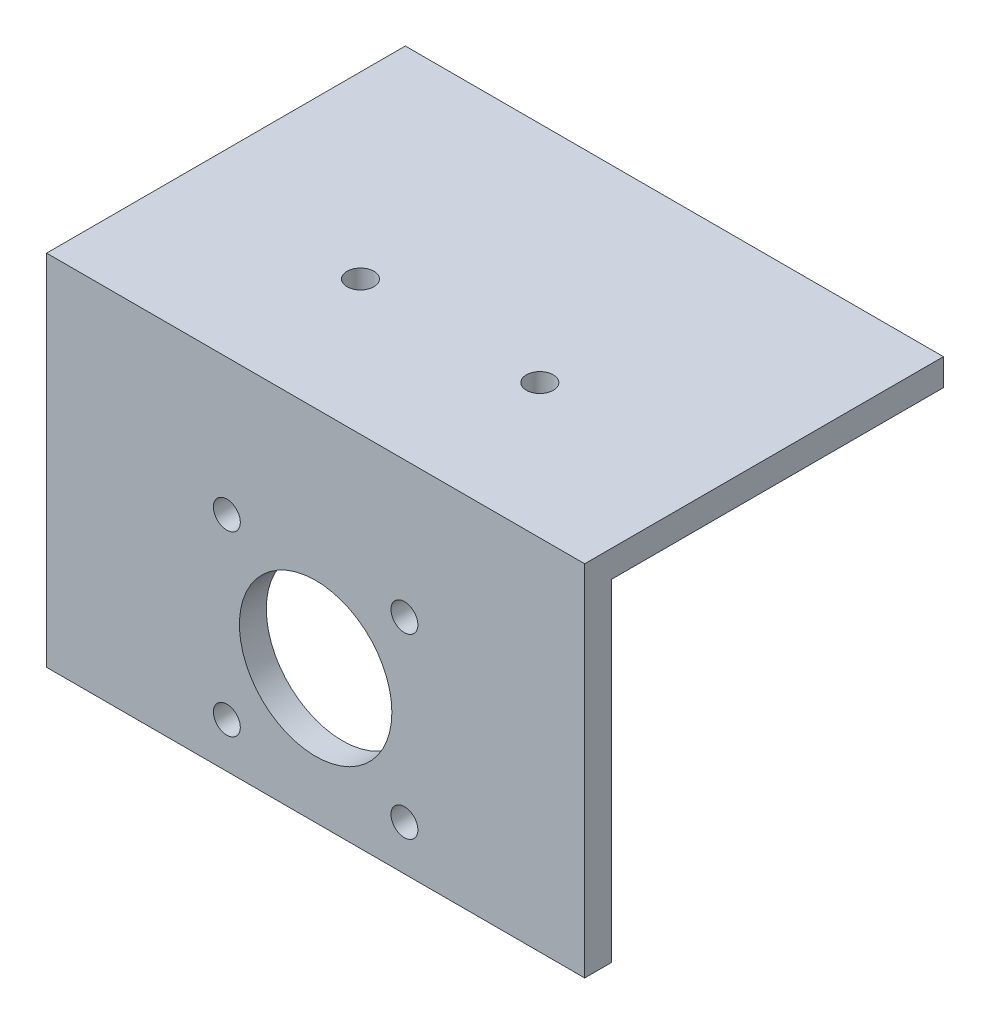
SolidWorks part; units mm, degrees
ref_plane "Front Plane" through (0, 0, 0) normal (0, 0, 1) x (1, 0, 0)
ref_plane "Top Plane" through (0, 0, 0) normal (0, 1, 0) x (1, 0, 0)
ref_plane "Right Plane" through (0, 0, 0) normal (1, 0, 0) x (0, 0, -1)
sketch "Sketch1" plane through (0, 0, 0) normal (1, 0, 0) x (0, 0, -1)
  line L0 (0, 0) -> (40, 0)
  line L1 (40, 0) -> (40, -3)
  line L2 (0, 0) -> (0, -40)
  line L3 (0, -40) -> (3, -40)
  line L4 (3, -40) -> (3, -3)
  line L5 (3, -3) -> (40, -3)
  point P3 (3, -3)
  dimension "D1" = 40
  dimension "D2" = 3
extrude "Boss-Extrude1" add sketch "Sketch1" along normal blind 30 and the other way blind 30
sketch "Sketch2" plane through (0, 0, 0) normal (0, 0, 1) x (1, 0, 0)
  line L0 (-30, -40) -> (30, -40) construction
  line L1 (-30, 0) -> (-30, -40) construction
  circle A0 centre (-9.8995, -15.201) radius 1.5
  circle A1 centre (9.8995, -15.201) radius 1.5
  circle A2 centre (-9.8995, -35) radius 1.5
  circle A3 centre (9.8995, -35) radius 1.5
  circle A4 centre (0, -25.101) radius 8.5
  point P12 (0, -40)
  point P13 (0, 0)
  dimension "D1" = 3
  dimension "D2" = 17
  dimension "D3" = 5
  dimension "D4" = 20.1005
  dimension "D5" = 19.799
  dimension "D6" = 19.799
  dimension "D7" = 9.899
extrude "Cut-Extrude1" cut sketch "Sketch2" against normal blind 30
sketch "Sketch3" plane through (0, 0, 0) normal (0, 1, 0) x (1, 0, 0)
  line L0 (-30, 40) -> (-30, 0) construction
  line L1 (-30, 0) -> (30, 0) construction
  circle A0 centre (-10, 15) radius 1.5
  circle A1 centre (10, 15) radius 1.5
  point P6 (0, 0)
  dimension "D1" = 3
  dimension "D2" = 20
  dimension "D3" = 20
  dimension "D4" = 15
extrude "Cut-Extrude2" cut sketch "Sketch3" against normal blind 30
